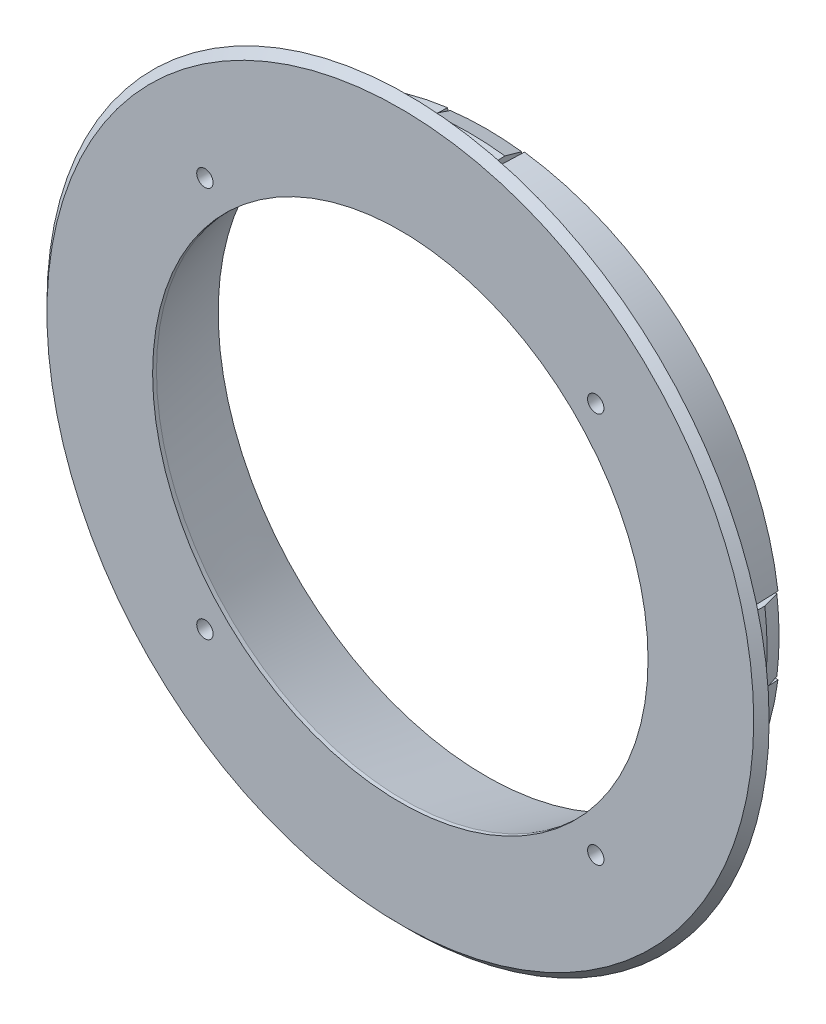
SolidWorks part; units mm, degrees
ref_plane "Спереди" through (0, 0, 0) normal (0, 0, 1) x (1, 0, 0)
ref_plane "Сверху" through (0, 0, 0) normal (0, 1, 0) x (1, 0, 0)
ref_plane "Справа" through (0, 0, 0) normal (1, 0, 0) x (0, 0, -1)
sketch "Main_profile" plane through (0, 0, 0) normal (0, 1, 0) x (1, 0, 0)
  line L0 (0, -21.597) -> (0, 33.5055) construction
  line L1 (-73.4, 0) -> (-62.45, 0)
  line L2 (-51.4493, 0.8) -> (-55.6294, 17.8)
  line L3 (-55.6294, 17.8) -> (-61.15, 17.8)
  line L4 (-61.15, 17.8) -> (-61.8, 1.6)
  line L5 (-61.8, 1.6) -> (-75, 1.6)
  line L6 (-75, 1.6) -> (-73.4, 0)
  line L7 (-62.45, 0) -> (-62.45, 0.8)
  line L8 (-62.45, 0.8) -> (-51.4493, 0.8)
  line L9 (-62.45, 0) -> (-51.4493, 0)
  line L10 (-51.4493, 0) -> (-51.4493, 0.8)
  line L13 (-60.8632, 17.8) -> (-62, 14.1731)
  line L14 (-62, 14.1731) -> (-61.6193, 6.1038)
  line L15 (-60.8632, 17.8) -> (-59.6437, 17.8)
  line L16 (-59.6437, 17.8) -> (-59.6437, 5.4963)
  line L17 (-59.6437, 5.4963) -> (-59.2437, 5.4963)
  line L18 (-59.2437, 5.4963) -> (-58.6437, 17.8)
  line L19 (-59.6437, 5.4963) -> (-61.6437, 5.4963)
  point P4 (-54.6636, 18.6)
  point P14 (-55.6294, 18.6)
  dimension "D1" = 122.3
  dimension "D2" = 123.6
  dimension "D3" = 16.2
  dimension "D4" = 150
  dimension "D5" = 45
  dimension "D6" = 1.6
  dimension "D7" = 124.9
  dimension "D8" = 0.8
  dimension "D11" = 0.4
  dimension "D12" = 0.2
  dimension "D13" = 2
  dimension "D14" = 1
revolve "Main_body" add sketch "Main_profile" angle 360 about L0 region at (-58.4292, 0, -6.4612) region at (-56.9496, 0, -0.4) region at (-60.5222, 0, -11.3166) region at (-59.2722, 0, -12.527) region at (-61.0684, 0, -17.4502)
revolve "clamp_cutoff" cut sketch "Эскиз1<8>" angle 15 mid plane about L0 region at (-60.5222, 0, -11.3166) region at (-59.2722, 0, -12.527) region at (-61.0684, 0, -17.4502)
sketch "Эскиз1<8>" plane through (0, 0, 0) normal (0, 1, 0) x (1, 0, 0) same geometry as "Main_profile"
revolve "Clamp_body" add sketch "Эскиз1<10>" angle 14 mid plane about L0 region at (-60.5222, 0, -11.3166) region at (-61.6038, 0, -12.3425)
sketch "Эскиз1<10>" plane through (0, 0, 0) normal (0, 1, 0) x (1, 0, 0) same geometry as "Main_profile"
pattern_circular "Clamp_array" count 4 over 360 about axis through (0, 0, -17.8) along (0, 0, 1) of "clamp_cutoff", "Clamp_body"
ref_plane "45" through (0, 0, 0) normal (0.7071, 0.7071, 0) x (0, 0, -1)
sketch "Hole_profile" plane through (0, 0, 0) normal (0.7071, 0.7071, 0) x (0, 0, -1)
  line L0 (17.8, 55.6294) -> (0.8, 51.4493)
  line L1 (0.8, -51.4493) -> (17.8, -55.6294)
  line L2 (0.8, -51.4493) -> (17.8, -55.6294)
  line L3 (17.8, 55.6294) -> (0.8, 51.4493)
  line L4 (1.6, 61.8) -> (17.8, 61.15)
  line L5 (17.8, -61.15) -> (1.6, -61.8)
  line L6 (17.8, -61.15) -> (1.6, -61.8)
  line L7 (1.6, 61.8) -> (17.8, 61.15)
  line L8 (17.8, 61.15) -> (17.8, 55.6294)
  line L9 (17.8, -55.6294) -> (17.8, -61.15)
  line L10 (17.8, -55.6294) -> (17.8, -61.15)
  line L11 (17.8, 61.15) -> (17.8, 55.6294)
  line L15 (0.8, -62.45) -> (0.8, -51.4493)
  line L16 (0, -73.4) -> (0, -51.4493)
  line L17 (0, 51.4493) -> (0, 73.4)
  line L18 (0, 51.4493) -> (0, 73.4)
  line L19 (0, -73.4) -> (0, -51.4493)
  line L22 (0, -51.4493) -> (0.8, -62.45)
  line L24 (-2.269, 57.4) -> (9.3566, 57.4) construction
  line L25 (-21.597, 0) -> (33.5055, 0) construction
  line L26 (0, 59.1) -> (12.9215, 58.6)
  line L27 (12.9215, 58.6) -> (15, 57.4)
  line L28 (15, 57.4) -> (0, 57.4)
  line L29 (0, 57.4) -> (0, 59.1)
  point P22 (0, 0)
  dimension "D1" = 57.4
  dimension "D2" = 3.4
  dimension "D3" = 15
  dimension "D4" = 2.4
  dimension "D5" = 30
revolve "Hole" cut sketch "Hole_profile" angle 360 about L24 region at (-41.091, 41.091, -6.5591)
pattern_circular "Holes_array" count 4 over 360 about axis through (0, 0, 0) along (0, 0, 1) of "Hole"
